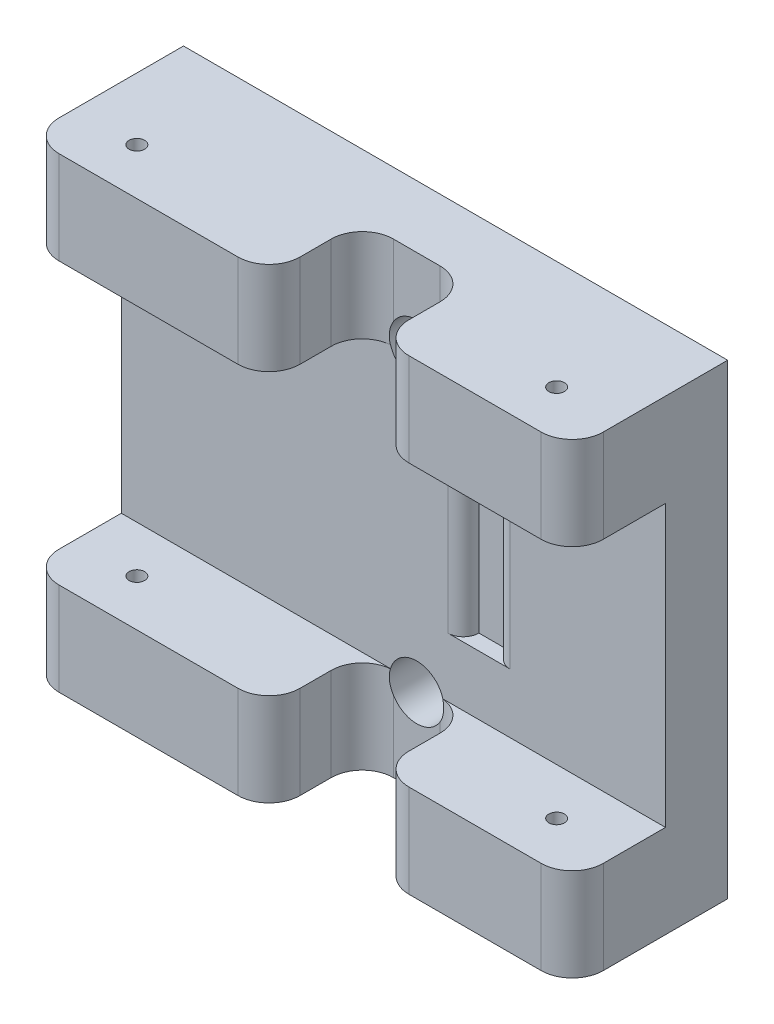
SolidWorks part; units mm, degrees
ref_plane "Front Plane" through (0, 0, 0) normal (0, 0, 1) x (1, 0, 0)
ref_plane "Top Plane" through (0, 0, 0) normal (0, 1, 0) x (1, 0, 0)
ref_plane "Right Plane" through (0, 0, 0) normal (1, 0, 0) x (0, 0, -1)
sketch "SketchButtom" plane through (0, 0, 0) normal (0, 0, 1) x (1, 0, 0)
  line L0 (-17.5, 15) -> (17.5, 15)
  line L1 (17.5, 15) -> (17.5, -15)
  line L2 (17.5, -15) -> (-17.5, -15)
  line L3 (-17.5, -15) -> (-17.5, 15)
  dimension "D1" = 30
  dimension "D2" = 35
  dimension "D3" = 15
  dimension "D4" = 17.5
sketch "SketchFingerRoom" plane through (0, 0, 0) normal (0, 0, 1) x (1, 0, 0)
  line L1 (5, 9.024) -> (17.5, 9.024)
  line L2 (17.5, -9.024) -> (17.5, 9.024)
  line L3 (-17.5, 15) -> (17.5, 15) construction
  line L4 (5, 15) -> (-2, 15)
  line L5 (-2, 15) -> (-2, 9.024)
  line L6 (-2, 9.024) -> (-17.5, 9.024)
  line L7 (-17.5, -15) -> (-17.5, 15) construction
  line L8 (-17.5, 9.024) -> (-17.5, -9.024)
  line L9 (-17.5, -9.024) -> (-2, -9.024)
  line L10 (-2, -9.024) -> (-2, -15)
  line L11 (17.5, -15) -> (-17.5, -15) construction
  line L12 (-2, -15) -> (5, -15)
  line L20 (17.5, 15) -> (17.5, -15) construction
  line L22 (5, 15) -> (5, 9.024)
  line L23 (5, -9.024) -> (17.5, -9.024)
  line L25 (5, -15) -> (5, -9.024)
  dimension "D1" = 15.5
  dimension "D2" = 18.048
  dimension "D3" = 12.5
  dimension "D4" = 5.976
extrude "BossExtrudeButtom" add sketch "SketchButtom" along normal blind 10
extrude "CutExtrudeFingerRoom" cut sketch "SketchFingerRoom" along normal blind 6 from offset 4
fillet "FilletTop" radius 2 12 edges at (-2, 12.012, 4) (-2, -12.012, 4) (5, -12.012, 4) (5, 12.012, 4) (-17.5, 12.012, 10) (-17.5, -12.012, 10) (-2, -12.012, 10) (5, -12.012, 10) (5, 12.012, 10) (17.5, 12.012, 10) (17.5, -12.012, 10) (-2, 12.012, 10)
sketch "SketchFingerShaft" plane through (0, 0, 0) normal (0, 1, 0) x (1, 0, 0)
  line L0 (-17.5, 0) -> (17.5, 0) construction
  line L1 (17.5, -8) -> (17.5, 0) construction
  line L2 (-17.5, -8) -> (-17.5, 0) construction
  circle A0 centre (-13.5, -7) radius 0.5
  circle A1 centre (13.5, -7) radius 0.5
  dimension "D5" = 1
  dimension "D6" = 1
  dimension "D1" = 7
  dimension "D2" = 7
  dimension "D3" = 4
  dimension "D4" = 4
extrude "CutExtrudeFingerShaft" cut sketch "SketchFingerShaft" against normal through all both and the other way through all
sketch "Sketch12" plane through (0, 0, 0) normal (0, 0, 1) x (1, 0, 0)
  line L0 (6.5, 5.2) -> (6.5, -5.2)
  line L1 (6.5, -5.2) -> (4.5, -5.2)
  line L2 (4.5, -5.2) -> (4.5, 5.2)
  line L3 (4.5, 5.2) -> (6.5, 5.2)
  line L4 (17.5, -9.024) -> (17.5, 9.024) construction
  line L5 (3, 15) -> (0, 15) construction
  line L6 (0, -15) -> (3, -15) construction
  point P6 (1.5, -15)
  dimension "D1" = 9.8
  dimension "D2" = 9.8
  dimension "D3" = 2
  dimension "D4" = 11
extrude "CutExtrudeSensorRoom" cut sketch "Sketch12" along normal blind 3 from offset 3
fillet "FilletSensorRoom" radius 1 2 edges at (4.5, 0, 4) (6.5, 0, 4)
sketch "SketchFixtureHoles" plane through (0, 0, 0) normal (0, 0, 1) x (1, 0, 0)
  line L0 (1.5, -9.5) -> (1.5, 9.5) construction
  line L2 (1.5, -9.5) -> (1.5, -15) construction
  line L3 (-17.5, -15) -> (17.5, -15) construction
  line L4 (1.5, 9.5) -> (1.5, 15) construction
  line L5 (17.5, 15) -> (-17.5, 15) construction
  line L6 (1.5, 0) -> (17.5, 0) construction
  line L7 (17.5, -15) -> (17.5, 15) construction
  circle A0 centre (1.5, -9.5) radius 1.75
  circle A1 centre (1.5, 9.5) radius 1.75
  dimension "D3" = 3.5
  dimension "D1" = 19
  dimension "D2" = 16
extrude "CutExtrudeFixtureHoles" cut sketch "SketchFixtureHoles" against normal mid plane 10
